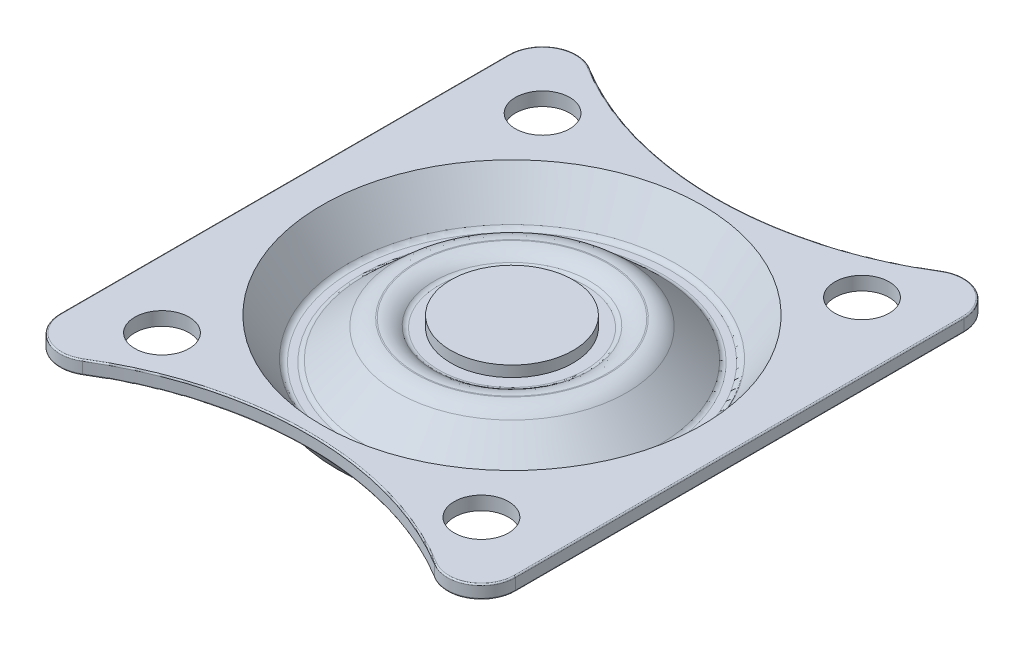
SolidWorks part; units mm, degrees
ref_plane "Alzado" through (0, 0, 0) normal (0, 0, 1) x (1, 0, 0)
ref_plane "Planta" through (0, 0, 0) normal (0, 1, 0) x (1, 0, 0)
ref_plane "Vista lateral" through (0, 0, 0) normal (1, 0, 0) x (0, 0, -1)
sketch "Croquis1" plane through (0, 0, 0) normal (0, 1, 0) x (1, 0, 0)
  line L0 (0, 15) -> (17.2343, 15) construction
  line L2 (-16.75, -16.5) -> (-16.75, 16.5)
  line L4 (16.75, -16.5) -> (16.75, 16.5)
  line L5 (-16.75, -19) -> (16.75, 19) construction
  line L6 (-16.75, 19) -> (16.75, -19) construction
  line L7 (0, 0) -> (16.75, 0) construction
  line L8 (0, 0) -> (0, 22.221) construction
  arc A0 (-12.949, 18.6348) -> (12.949, 18.6348) centre (0, 39.8828) ccw
  arc A1 (-12.949, 18.6348) -> (-16.75, 16.5) centre (-14.25, 16.5) ccw
  arc A2 (12.949, 18.6348) -> (16.75, 16.5) centre (14.25, 16.5) cw
  arc A3 (-12.949, -18.6348) -> (12.949, -18.6348) centre (0, -39.8828) cw
  arc A4 (-12.949, -18.6348) -> (-16.75, -16.5) centre (-14.25, -16.5) cw
  arc A5 (12.949, -18.6348) -> (16.75, -16.5) centre (14.25, -16.5) ccw
  circle A6 centre (-11.75, -14) radius 2
  circle A7 centre (-11.75, 14) radius 2
  circle A8 centre (11.75, -14) radius 2
  circle A9 centre (11.75, 14) radius 2
  point P0 (0, 0)
  dimension "D4" = 5
  dimension "D5" = 4
  dimension "D6" = 5
  dimension "D1" = 33.5
  dimension "D2" = 38
extrude "Extruir1" add sketch "Croquis1" along normal blind 1
sketch "Croquis2" plane through (0, 1, 0) normal (0, 1, 0) x (1, 0, 0)
  circle A0 centre (0, 0) radius 4
  dimension "D1" = 8
sketch "Croquis4" plane through (0, 1, 0) normal (0, 1, 0) x (1, 0, 0)
  circle A0 centre (0, 0) radius 14
  dimension "D1" = 28
extrude "Extruir3" cut sketch "Croquis4" against normal through all
sketch "Croquis3" plane through (0, 0, 0) normal (0, 0, 1) x (1, 0, 0)
  line L0 (-12.949, 0) -> (12.949, 0) construction
  line L1 (-14.5277, 0) -> (-12.4767, -3)
  line L2 (-10.5625, -3) -> (-12.4767, -3)
  line L3 (-5.949, 0.8) -> (-5.75, 0.2)
  line L4 (12.949, 1) -> (-12.949, 1) construction
  line L5 (-10.5625, -3) -> (-7.4816, -0.2)
  line L6 (-7.4816, -0.2) -> (-6.6709, -0.2)
  line L7 (-10.949, -2) -> (-7.8682, 0.8)
  line L8 (-7.8682, 0.8) -> (-5.949, 0.8)
  line L9 (-12.949, -0.5373) -> (-11.949, -2)
  line L10 (-10.949, -2) -> (-11.949, -2)
  line L11 (-6.6709, -0.2) -> (-6.4719, -0.8)
  line L12 (-6.4719, -0.8) -> (0, -0.8)
  line L13 (0, -0.8) -> (0, 0.2)
  line L14 (0, 0.2) -> (0, 12.6983) construction
  line L15 (-14, 1) -> (-14, 0)
  line L17 (-12.949, -0.5373) -> (-14, 1)
  line L18 (-13.7745, -1.1017) -> (-12.4767, -3) construction
  line L19 (-16.75, 0) -> (-12.949, 0) construction
  line L20 (-5.75, 0.2) -> (0, 0.2)
  line L21 (14, 1) -> (-14, 1) construction
  line L23 (-14, 0) -> (-14.5277, 0)
  dimension "D1" = 2
  dimension "D2" = 5.75
  dimension "D3" = 5
  dimension "D4" = 1
  dimension "D5" = 0.2
  dimension "D6" = 2
  dimension "D7" = 1
revolve "Revolución1" add sketch "Croquis3" angle 360 about L14
fillet "Redondeo1" radius 2 2 edges at (0, -3, -10.5625) (0, -3, -12.4767)
fillet "Redondeo2" radius 0.5 3 edges at (0, -2, -11.949) (0, 0.2, -5.75) (0, -2, -10.949)
fillet "Redondeo3" radius 2 2 edges at (0, 0.8, -5.949) (0, 0.8, -7.8682)
fillet "Redondeo6" radius 0.1 16 edges at (-16.75, 0, 0) (-15.4742, 0, -18.6797) (0, 0, -15) (15.4742, 0, -18.6797) (16.75, 0, 0) (15.4742, 0, 18.6797) (0, 0, 15) (-15.4742, 1, -18.6797) (0, 1, -15) (15.4742, 1, -18.6797) (16.75, 1, 0) (15.4742, 1, 18.6797) (0, 1, 15) (-15.4742, 1, 18.6797) (-15.4742, 0, 18.6797) (-16.75, 1, 0)
extrude "Extruir5" cut sketch "Croquis2" against normal through all
sketch "Croquis5" plane through (0, 1, 0) normal (0, 1, 0) x (1, 0, 0)
  circle A0 centre (0, 0) radius 4.5
  dimension "D1" = 9
extrude "Extruir6" add sketch "Croquis5" against normal blind 6
sketch "Croquis6" plane through (0, -5, 0) normal (0, -1, 0) x (1, 0, 0)
  circle A0 centre (0, 0) radius 5
  dimension "D1" = 10
extrude "Extruir7" add sketch "Croquis6" along normal blind 1
fillet "Redondeo7" radius 0.5 1 edges at (0, -6, -5)
sketch "Croquis7" plane through (0, 0, 0) normal (0, 0, 1) x (1, 0, 0)
  line L0 (-7.5801, -0.4418) -> (-7.5801, -3.4418)
  arc A0 (-7.5801, -0.4418) -> (-7.5801, -3.4418) centre (-7.5801, -1.9418) ccw
  dimension "D1" = 1.5
revolve "Revolución2" add sketch "Croquis7" angle 360 about L0
ref_axis "Eje2" through (0, -6.35, 0) along (0, 1, 0)
pattern_circular "MatrizC3" count 16 over 360 about axis through (0, -6.35, 0) along (0, 1, 0) of bodies 111
